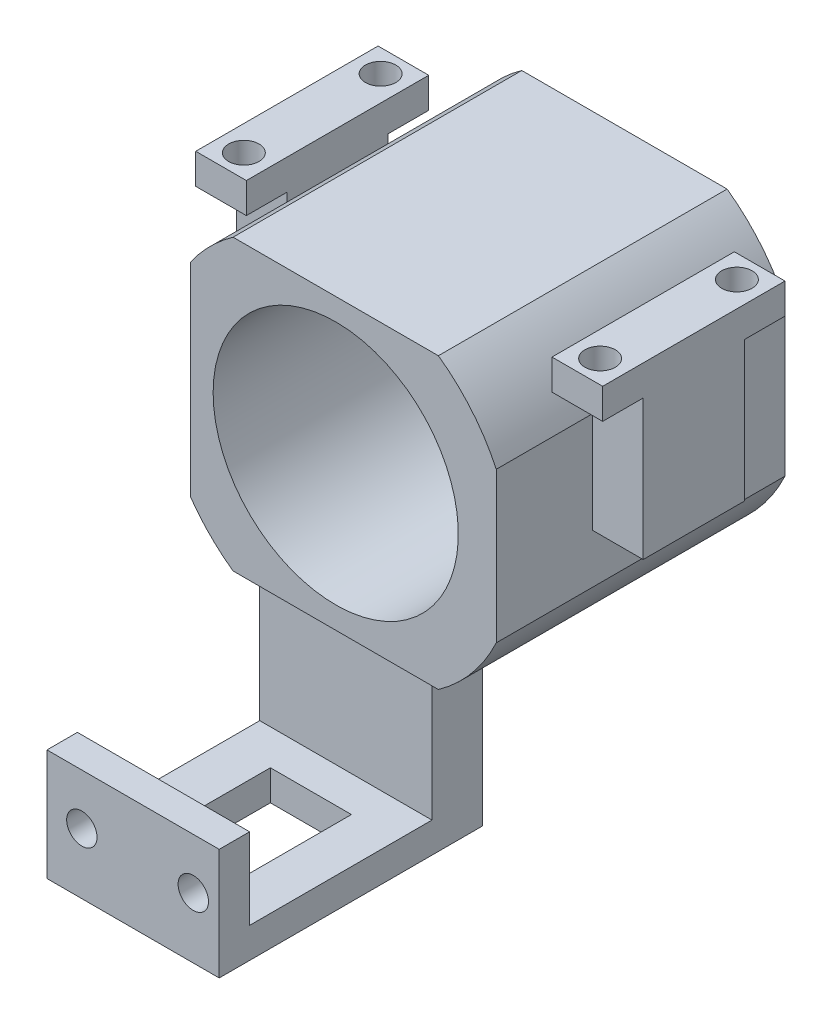
SolidWorks part; units mm, degrees
ref_plane "Front Plane" through (0, 0, 0) normal (0, 0, 1) x (1, 0, 0)
ref_plane "Top Plane" through (0, 0, 0) normal (0, 1, 0) x (1, 0, 0)
ref_plane "Right Plane" through (0, 0, 0) normal (1, 0, 0) x (0, 0, -1)
sketch "Sketch1" plane through (0, 0, 0) normal (0, 0, 1) x (1, 0, 0)
  line L1 (10.1345, 14.2668) -> (-10.1345, 14.2668)
  line L2 (10.135, -14.2665) -> (-10.135, -14.2665)
  line L3 (15.8502, 7.4176) -> (15.8502, -7.4176)
  line L4 (-14.3183, 10.0617) -> (-14.3183, -10.0617)
  circle A2 centre (0, 0) radius 12.1
  arc A3 (-10.1345, 14.2668) -> (-14.3183, 10.0617) centre (0, 0) ccw
  arc A4 (15.8502, 7.4176) -> (10.1345, 14.2668) centre (0, 0) ccw
  arc A5 (10.135, -14.2665) -> (15.8502, -7.4176) centre (0, 0) ccw
  arc A6 (-14.3183, -10.0617) -> (-10.135, -14.2665) centre (0, 0) ccw
  point P7 (0, 15.0991)
  dimension "D1" = 35
  dimension "D2" = 24.2
  dimension "D3" = 20.2691
  dimension "D4" = 20.27
  dimension "D5" = 14.8352
  dimension "D6" = 20.1233
extrude "Boss-Extrude1" add sketch "Sketch1" along normal blind 3.5 contours A2
extrude "Boss-Extrude2" add sketch "Sketch1<4>" along normal blind 28.5
sketch "Sketch1<4>" plane through (0, 0, 0) normal (0, 0, 1) x (1, 0, 0) same geometry as "Sketch1"
sketch "Sketch3" plane through (0, 0, 0) normal (0, 0, -1) x (-1, 0, 0)
  line L0 (-10.1345, 14.2668) -> (10.1345, 14.2668) construction
  line L1 (-2.7, 10.5168) -> (1.8, 10.5168)
  line L2 (-2.7, 10.5168) -> (-2.7, 8.2191)
  line L3 (-2.7, 8.2191) -> (1.8, 8.2191)
  line L4 (1.8, 10.5168) -> (1.8, 8.2191)
  line L6 (55, 0) -> (-55, 0) construction
  line L7 (-2.7, -8.2191) -> (1.8, -8.2191)
  line L8 (1.8, -10.5168) -> (1.8, -8.2191)
  line L9 (-2.7, -10.5168) -> (1.8, -10.5168)
  line L10 (-2.7, -10.5168) -> (-2.7, -8.2191)
  arc A1 (14.3183, 10.0617) -> (10.1345, 14.2668) centre (0, 0) ccw construction
  dimension "D1" = 4.5
  dimension "D2" = 2.2977
  dimension "D3" = 3.75
  dimension "D4" = 1.8
extrude "Cut-Extrude1" cut sketch "Sketch3" against normal through all both and the other way through all
sketch "Sketch5" plane through (0, 0, 28.5) normal (0, 0, 1) x (1, 0, 0)
  line L0 (-10.135, -14.2665) -> (10.135, -14.2665)
  arc A0 (-10.1345, 14.2668) -> (-14.3183, 10.0617) centre (0, 0) ccw construction
  dimension "D1" = 20.27
sketch "Sketch6" plane through (0, -14.2665, 0) normal (0, -1, 0) x (-1, 0, 0)
  line L0 (10.135, -28.5) -> (-10.135, -28.5) construction
  line L1 (8.5, -22.5) -> (-8.5, -22.5)
  line L2 (8.5, -22.5) -> (8.5, -27.5)
  line L3 (8.5, -27.5) -> (-8.5, -27.5)
  line L4 (-8.5, -22.5) -> (-8.5, -27.5)
  line L6 (10.135, -28.5) -> (10.135, 0) construction
  dimension "D1" = 5
  dimension "D2" = 17
  dimension "D3" = 1
  dimension "D4" = 1.635
extrude "Boss-Extrude4" add sketch "Sketch6" along normal blind 15.48
sketch "Sketch7" plane through (0, 0, 27.5) normal (0, 0, 1) x (1, 0, 0)
  line L1 (-8.5, -29.7465) -> (8.5, -29.7465)
  line L2 (-8.5, -29.7465) -> (-8.5, -26.7465)
  line L3 (-8.5, -26.7465) -> (8.5, -26.7465)
  line L4 (8.5, -29.7465) -> (8.5, -26.7465)
  dimension "D1" = 17
  dimension "D2" = 3
extrude "Boss-Extrude5" add sketch "Sketch7" along normal blind 21
sketch "Sketch9" plane through (0, 0, 48.5) normal (0, 0, 1) x (1, 0, 0)
  circle A0 centre (-5.06, -23.7513) radius 1.5
  circle A1 centre (5.94, -23.7513) radius 1.5
  dimension "D1" = 3
  dimension "D2" = 3
ref_plane "Plane1" through (10.1345, 14.2668, 28.5) normal (0, 0, -1) x (-1, 0, 0)
sketch "Sketch10" plane through (0, -29.7465, 0) normal (0, -1, 0) x (-1, 0, 0)
  line L0 (8.5, -48.5) -> (-8.5, -48.5) construction
  line L1 (3.9496, -46) -> (-4.0504, -46)
  line L2 (3.9496, -46) -> (3.9496, -31)
  line L3 (3.9496, -31) -> (-4.0504, -31)
  line L4 (-4.0504, -46) -> (-4.0504, -31)
  line L5 (8.5, -48.5) -> (8.5, -22.5) construction
  dimension "D1" = 15
  dimension "D2" = 8
  dimension "D3" = 2.5
  dimension "D4" = 4.5504
extrude "Cut-Extrude4" cut sketch "Sketch10" against normal mid plane 10
sketch "Sketch12" plane through (0, -26.7465, 0) normal (0, 1, 0) x (1, 0, 0)
  line L0 (8.5, -48.5) -> (8.5, -27.5) construction
  line L1 (-8.5, -48.5) -> (8.5, -48.5)
  line L2 (-8.5, -48.5) -> (-8.5, -45.5)
  line L3 (-8.5, -45.5) -> (8.5, -45.5)
  line L4 (8.5, -48.5) -> (8.5, -45.5)
  dimension "D1" = 3
extrude "Boss-Extrude8" add sketch "Sketch12" along normal blind 8
extrude "Cut-Extrude5" cut sketch "Sketch9" against normal mid plane 8
sketch "Sketch13" plane through (-14.3183, 0, 0) normal (-1, 0, 0) x (0, 0, 1)
  line L0 (28.5, -10.0617) -> (0, -10.0617) construction
  line L1 (9, 2.3087) -> (19, 2.3087)
  line L2 (9, 2.3087) -> (9, -1.6913)
  line L3 (9, -1.6913) -> (19, -1.6913)
  line L4 (19, 2.3087) -> (19, -1.6913)
  line L7 (0, 10.0617) -> (0, -10.0617) construction
  dimension "D1" = 10
  dimension "D2" = 4
  dimension "D3" = 8.3704
  dimension "D4" = 9
extrude "Boss-Extrude9" add sketch "Sketch13" along normal blind 5
sketch "Sketch15" plane through (0, 2.3087, 0) normal (0, 1, 0) x (1, 0, 0)
  line L1 (-14.3183, -19) -> (-19.3183, -19)
  line L2 (-14.3183, -19) -> (-14.3183, -9)
  line L3 (-14.3183, -9) -> (-19.3183, -9)
  line L4 (-19.3183, -19) -> (-19.3183, -9)
extrude "Boss-Extrude10" add sketch "Sketch15" along normal blind 11.96
sketch "Sketch16" plane through (0, 0, 9) normal (0, 0, -1) x (-1, 0, 0)
  line L0 (19.3183, 14.2687) -> (19.3183, -1.6913) construction
  line L1 (14.3183, 14.2687) -> (19.3183, 14.2687)
  line L2 (14.3183, 14.2687) -> (14.3183, 11.2687)
  line L3 (14.3183, 11.2687) -> (19.3183, 11.2687)
  line L4 (19.3183, 14.2687) -> (19.3183, 11.2687)
  dimension "D1" = 3
sketch "Sketch17" plane through (0, 0, 19) normal (0, 0, 1) x (1, 0, 0)
  line L1 (-19.3183, 14.2687) -> (-14.3183, 14.2687)
  line L2 (-19.3183, 14.2687) -> (-19.3183, 11.2687)
  line L3 (-19.3183, 11.2687) -> (-14.3183, 11.2687)
  line L4 (-14.3183, 14.2687) -> (-14.3183, 11.2687)
extrude "Boss-Extrude11" add sketch "Sketch17" along normal blind 4
extrude "Boss-Extrude12" add sketch "Sketch16" along normal blind 4
ref_plane "Plane2" through (-8.5, -29.7465, 22.5) normal (0, 0, -1) x (-1, 0, 0)
sketch "Sketch20" plane through (15.8502, 0, 0) normal (1, 0, 0) x (0, 0, -1)
  line L1 (-19, 1.4524) -> (-9, 1.4524)
  line L2 (-19, 1.4524) -> (-19, -2.5476)
  line L3 (-19, -2.5476) -> (-9, -2.5476)
  line L4 (-9, 1.4524) -> (-9, -2.5476)
  line L7 (-28.5, -7.4176) -> (0, -7.4176) construction
  line L8 (0, -7.4176) -> (0, 7.4176) construction
  dimension "D1" = 10
  dimension "D2" = 4
  dimension "D3" = 4.87
  dimension "D4" = 9
extrude "Boss-Extrude13" add sketch "Sketch20" along normal blind 5
ref_plane "Plane3" through (15.8502, 1.4524, 19) normal (-1, 0, 0) x (0, 0, 1)
sketch "Sketch22" plane through (0, 1.4524, 0) normal (0, 1, 0) x (1, 0, 0)
  line L1 (15.8502, -19) -> (20.8502, -19)
  line L2 (15.8502, -19) -> (15.8502, -9)
  line L3 (15.8502, -9) -> (20.8502, -9)
  line L4 (20.8502, -19) -> (20.8502, -9)
extrude "Boss-Extrude14" add sketch "Sketch22" along normal blind 12.81
sketch "Sketch25" plane through (0, 0, 9) normal (0, 0, -1) x (-1, 0, 0)
  line L0 (-15.8502, 14.2624) -> (-15.8502, 7.4176) construction
  line L1 (-20.8502, 14.2624) -> (-15.8502, 14.2624)
  line L2 (-20.8502, 14.2624) -> (-20.8502, 11.2624)
  line L3 (-20.8502, 11.2624) -> (-15.8502, 11.2624)
  line L4 (-15.8502, 14.2624) -> (-15.8502, 11.2624)
  dimension "D1" = 3
sketch "Sketch26" plane through (0, 0, 19) normal (0, 0, 1) x (1, 0, 0)
  line L1 (15.8502, 14.2624) -> (20.8502, 14.2624)
  line L2 (15.8502, 14.2624) -> (15.8502, 11.2624)
  line L3 (15.8502, 11.2624) -> (20.8502, 11.2624)
  line L4 (20.8502, 14.2624) -> (20.8502, 11.2624)
extrude "Boss-Extrude15" add sketch "Sketch26" along normal blind 4
extrude "Boss-Extrude16" add sketch "Sketch25" along normal blind 4
sketch "Sketch27" plane through (0, 14.2624, 0) normal (0, 1, 0) x (1, 0, 0)
  line L0 (20.8502, -23) -> (15.8502, -23) construction
  line L1 (15.8502, -5) -> (20.8502, -5) construction
  line L2 (15.8502, -5) -> (15.8502, -23) construction
  circle A0 centre (18.3502, -20.75) radius 1.5
  circle A1 centre (18.3502, -7.25) radius 1.5
  dimension "D1" = 2.25
  dimension "D2" = 2.25
  dimension "D4" = 3
  dimension "D5" = 3
  dimension "D3" = 13.5
  dimension "D6" = 2.5
extrude "Cut-Extrude7" cut sketch "Sketch27" against normal through all both and the other way through all
sketch "Sketch28" plane through (0, 14.2687, 0) normal (0, 1, 0) x (1, 0, 0)
  line L0 (-19.3183, -5) -> (-14.3183, -5) construction
  line L1 (-19.3183, -5) -> (-19.3183, -23) construction
  line L2 (-14.3183, -23) -> (-19.3183, -23) construction
  circle A0 centre (-16.8183, -7.25) radius 1.5
  circle A1 centre (-16.8183, -20.75) radius 1.5
  dimension "D1" = 2.25
  dimension "D2" = 3
  dimension "D4" = 2.25
  dimension "D5" = 3
  dimension "D3" = 2.5
  dimension "D6" = 2.5
extrude "Cut-Extrude8" cut sketch "Sketch28" against normal through all both and the other way through all
